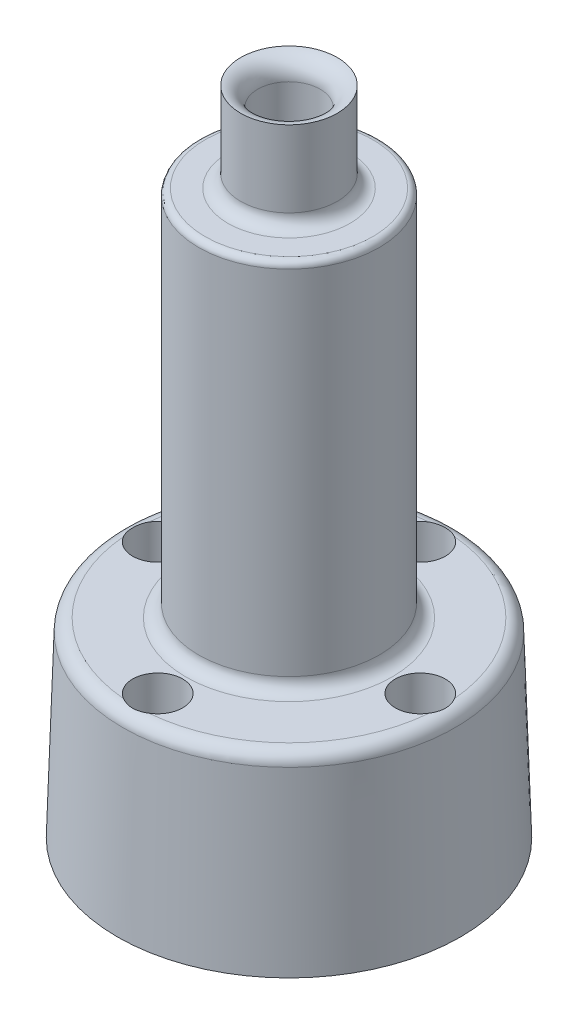
SolidWorks part; units mm, degrees
material "6061-T6 (SS)"
ref_plane "Front Plane" through (0, 0, 0) normal (0, 0, 1) x (1, 0, 0)
ref_plane "Top Plane" through (0, 0, 0) normal (0, 1, 0) x (1, 0, 0)
ref_plane "Right Plane" through (0, 0, 0) normal (1, 0, 0) x (0, 0, -1)
sketch "Sketch2" plane through (0, 0, 0) normal (0, 0, 1) x (1, 0, 0)
  line L0 (0, 0) -> (0, 10.9572) construction
  line L1 (0, 0) -> (6.858, 0)
  line L3 (1.9304, 26.035) -> (0, 26.035)
  line L4 (0, 26.035) -> (0, 0)
  line L5 (3.6068, 22.479) -> (3.6068, 7.62)
  line L6 (3.6068, 7.62) -> (6.6199, 7.62)
  line L7 (6.6199, 7.62) -> (6.858, 0)
  line L8 (1.9304, 26.035) -> (1.9304, 22.479)
  line L9 (1.9304, 22.479) -> (3.6068, 22.479)
  dimension "D1" = 13.716
  dimension "D2" = 26.035
  dimension "D3" = 1.79
  dimension "D4" = 7.62
  dimension "D5" = 7.2136
  dimension "D6" = 3.8608
  dimension "D7" = 3.556
revolve "Revolve1" add sketch "Sketch2" angle 360 about L0
fillet "Large Radii" radius 0.508 3 edges at (0, 7.62, -3.6068) (0, 22.479, -1.9304) (0, 7.62, -6.6199)
fillet "Small OD Radii" radius 0.254 1 edges at (0, 22.479, -3.6068)
sketch "Sketch5" plane through (0, 0, 0) normal (0, -1, 0) x (1, 0, 0)
  point P0 (0, 0)
hole_wizard "#42 (0.0935) LOX Inlet" positions "Sketch5" profile "Sketch6" hole size "Ø2.1" standard "ANSI Metric"
sketch "Sketch6" plane through (0, 0, 0) normal (1, 0, 0) x (0, 0, -1)
  line L0 (0, 0) -> (0, 9.5209)
  line L1 (0, 9.5209) -> (1.05, 8.89)
  line L2 (1.05, 8.89) -> (1.05, 0)
  line L5 (1.05, 0) -> (0, 0)
  line L10 (0, 9.5209) -> (-1.05, 8.89) construction
  line L11 (0, -6.35) -> (0, 107.95) construction
  dimension "Hole Dia." = 2.1
  dimension "Hole Depth" = 8.89
  dimension "Drill Angle" = 118
sketch "Sketch7" plane through (0, 26.035, 0) normal (0, 1, 0) x (1, 0, 0)
  point P0 (0, 0)
hole_wizard "1/8 (0.125) LOX Lead-in" positions "Sketch7" profile "Sketch8" hole size "Ø2.5" standard "ANSI Metric"
sketch "Sketch8" plane through (0, 26.035, 0) normal (1, 0, 0) x (0, 0, 1)
  line L0 (0, 0) -> (0, 17.8961)
  line L1 (0, 17.8961) -> (1.25, 17.145)
  line L2 (1.25, 17.145) -> (1.25, 0)
  line L5 (1.25, 0) -> (0, 0)
  line L10 (0, 17.8961) -> (-1.25, 17.145) construction
  line L11 (0, -6.35) -> (0, 107.95) construction
  dimension "Hole Dia." = 2.5
  dimension "Hole Depth" = 17.145
  dimension "Drill Angle" = 118
sketch "Sketch14" plane through (0, 7.62, 0) normal (0, 1, 0) x (1, 0, 0)
  line L1 (5.2451, 0) -> (3.6068, 0) construction
  circle A3 centre (0, 0) radius 3.6068 construction
  circle A4 centre (0, 0) radius 3.6068 construction
  point P12 (5.2451, 0)
  dimension "D1" = 1.6383
hole_wizard "Ø2.0 (2) Diameter Hole2" positions "Sketch14" profile "Sketch16" hole size "Ø2.0" standard "ANSI Metric"
sketch "Sketch16" plane through (5.2451, 7.62, 0) normal (1, 0, 0) x (0, 0, 1)
  line L0 (0, 0) -> (0, 5.4269)
  line L1 (0, 5.4269) -> (1, 4.826)
  line L2 (1, 4.826) -> (1, 0)
  line L5 (1, 0) -> (0, 0)
  line L10 (0, 5.4269) -> (-1, 4.826) construction
  line L11 (0, -6.35) -> (0, 107.95) construction
  dimension "Hole Dia." = 2
  dimension "Hole Depth" = 4.826
  dimension "Drill Angle" = 118
sketch "Sketch11" plane through (0, 0, 0) normal (0, 0, 1) x (1, 0, 0)
  line L0 (2.286, 0) -> (6.858, 4.572) construction
  line L1 (-6.858, 0) -> (6.858, 0) construction
  line L4 (2.286, -0.5303) -> (5.588, 2.7717)
  line L5 (5.3228, 3.0368) -> (2.0208, -0.2652)
  line L6 (5.588, 2.7717) -> (5.0577, 3.302) construction
  line L7 (5.588, 2.7717) -> (5.3228, 3.0368)
  line L8 (2.286, -0.5303) -> (1.7557, 0) construction
  line L9 (2.0208, -0.2652) -> (2.286, -0.5303)
  line L10 (-6.858, 0) -> (6.858, 0) construction
  dimension "D3" = 0.75
  dimension "D4" = 0.75
  dimension "D5" = 0.75
  dimension "D1" = 45
  dimension "D2" = 4.572
  dimension "D6" = 1.27
revolve "Fuel Hole" cut sketch "Sketch11" angle 360 about L5
sketch "Sketch12" plane through (0, 0, 0) normal (0, 0, 1) x (1, 0, 0)
  line L0 (5.3228, 3.0368) -> (2.0208, -0.2652) construction
  line L1 (5.3228, 3.0368) -> (2.0208, -0.2652) construction
  line L2 (2.7468, 0.4608) -> (2.0828, 0.6387)
  line L3 (2.7468, 0.4608) -> (2.9247, -0.2032) construction
  line L4 (2.0828, 0.6387) -> (1.2409, -0.2032)
  line L5 (1.2409, -0.2032) -> (2.0828, -1.0451) construction
  line L6 (2.0828, -1.0451) -> (2.9247, -0.2032) construction
  line L7 (-6.858, 0) -> (6.858, 0) construction
  line L8 (2.7468, 0.4608) -> (1.6619, -0.6241) construction
  line L9 (2.7468, 0.4608) -> (1.6619, -0.6241)
  line L10 (1.6619, -0.6241) -> (1.2409, -0.2032)
  dimension "D1" = 60
  dimension "D2" = 1.1906
  dimension "D3" = 0.2032
  dimension "D4" = 1.1906
revolve "Fuel Spot Drill" cut sketch "Sketch12" angle 360 about L9
pattern_circular "CirPattern1" count 4 over 360 about axis through (0, 0, 0) along (0, -1, 0) of "Fuel Hole", "Fuel Spot Drill", "Ø2.0 (2) Diameter Hole2"
fillet "Fillet1" radius 0.762 1 edges at (0, 26.035, 1.25)
equation "\"LOX Diameter\"= 2.1mm"
equation "\"Fuel Diameter\"= 0.75mm"
equation "\"Fuel Number\"= 4"
equation "\"D4@Sketch11\"=\"D3@Sketch11\""
equation "\"D5@Sketch11\"=\"D3@Sketch11\""
equation "\"D3@Sketch11\"=\"Fuel Diameter\""
equation "\"D1@CirPattern1\"=\"Fuel Number\""
